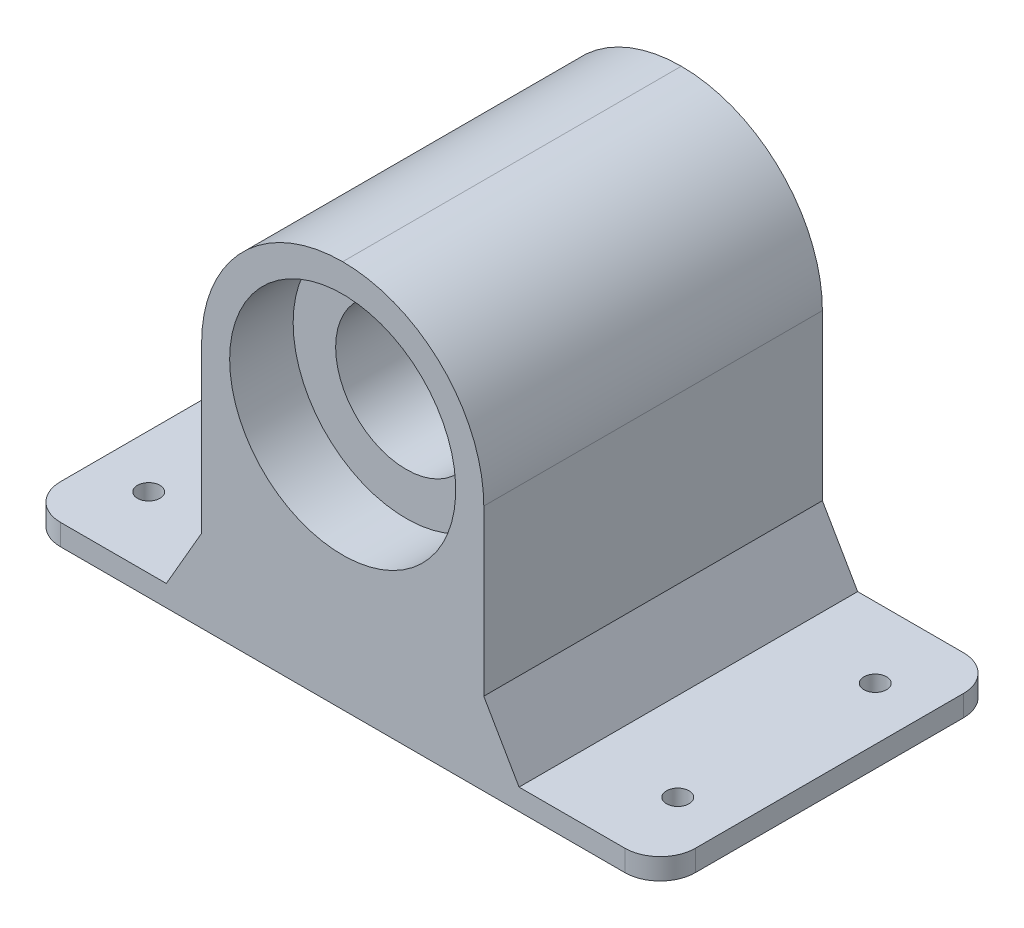
SolidWorks part; units mm, degrees
material "6061-T6 (SS)"
ref_plane "前视基准面" through (0, 0, 0) normal (0, 0, 1) x (1, 0, 0)
ref_plane "上视基准面" through (0, 0, 0) normal (0, 1, 0) x (1, 0, 0)
ref_plane "右视基准面" through (0, 0, 0) normal (1, 0, 0) x (0, 0, -1)
sketch "草图1" plane through (0, 0, 0) normal (0, 0, 1) x (1, 0, 0)
  line L0 (-20, -35) -> (-20, 0)
  line L2 (20, 0) -> (-20, 0) construction
  line L3 (-20, -35) -> (20, -35)
  line L4 (20, 0) -> (20, 20)
  line L5 (20, 20) -> (-20, 20)
  line L6 (-20, 0) -> (-20, 20)
  line L7 (20, -35) -> (20, 0)
  circle A1 centre (0, 0) radius 10
  dimension "D2" = 20
  dimension "D3" = 40
  dimension "D4" = 20
  dimension "D1" = 35
extrude "凸台-拉伸1" add sketch "草图1" along normal mid plane 48
sketch "草图4" plane through (0, 0, -24) normal (0, 0, -1) x (-1, 0, 0)
  circle A0 centre (0, 0) radius 16.025
  dimension "D1" = 32.05
extrude "切除-拉伸3" cut sketch "草图4" against normal blind 9
mirror "镜向1" about plane through (0, 0, 0) normal (0, 0, 1) of "切除-拉伸3"
ref_plane "基准面1" through (0, 0, 0) normal (-1, 0, 0) x (0, 0, 1)
sketch "草图5" plane through (20, 0, 0) normal (1, 0, 0) x (0, 0, -1)
  line L0 (24, -35) -> (24, 20) construction
  line L1 (-24, -35) -> (24, -35)
  line L2 (-24, -35) -> (-24, -32)
  line L3 (-24, -32) -> (24, -32)
  line L4 (24, -35) -> (24, -32)
  dimension "D1" = 3
extrude "凸台-拉伸2" add sketch "草图5" along normal blind 25
mirror "镜向2" about plane through (0, 0, 0) normal (-1, 0, 0) of "凸台-拉伸2"
chamfer "倒角1" distance 5 angle 60 2 edges at (-20, -32, 0) (20, -32, 0) first distance on face at (-32.5, -32, 0) first distance on face at (32.5, -32, 0)
sketch "草图7" plane through (0, -35, 0) normal (0, -1, 0) x (1, 0, 0)
  line L0 (37.5, 24) -> (37.5, -24) construction
  line L1 (-45, 24) -> (45, 24) construction
  line L2 (-45, -24) -> (45, -24) construction
  line L3 (0, 24) -> (0, -24) construction
  line L4 (45, 24) -> (45, -24) construction
  line L5 (-45, 0) -> (45, 0) construction
  line L6 (-45, 24) -> (-45, -24) construction
  circle A0 centre (37.5, 14) radius 1.6
  circle A1 centre (37.5, -14) radius 1.6
  circle A2 centre (-37.5, 14) radius 1.6
  circle A3 centre (-37.5, -14) radius 1.6
  dimension "D2" = 10
  dimension "D3" = 3.2
  dimension "D1" = 7.5
extrude "切除-拉伸4" cut sketch "草图7" against normal through all
fillet "圆角1" radius 20 2 edges at (20, 20, 0) (-20, 20, 0)
fillet "圆角2" radius 5 4 edges at (45, -33.5, 24) (45, -33.5, -24) (-45, -33.5, -24) (-45, -33.5, 24)
